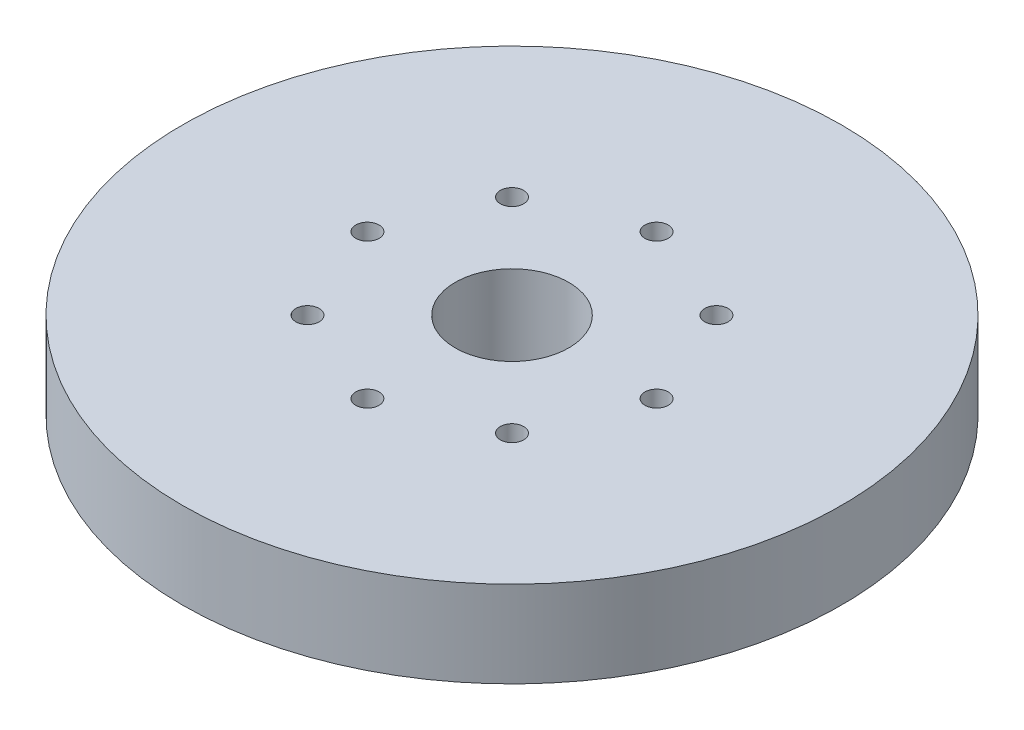
SolidWorks part; units mm, degrees
ref_plane "Front Plane" through (0, 0, 0) normal (0, 0, 1) x (1, 0, 0)
ref_plane "Top Plane" through (0, 0, 0) normal (0, 1, 0) x (1, 0, 0)
ref_plane "Right Plane" through (0, 0, 0) normal (1, 0, 0) x (0, 0, -1)
sketch "Sketch1" plane through (0, 0, 0) normal (0, 1, 0) x (1, 0, 0)
  circle A0 centre (0, 0) radius 72.5
  dimension "FLANGE_OD" = 145
extrude "Boss-Extrude1" add sketch "Sketch1" along normal blind 19
sketch "Sketch2" plane through (0, 0, 0) normal (0, 1, 0) x (1, 0, 0)
  circle A0 centre (0, 0) radius 12.5
  dimension "BORE_D" = 25
extrude "Cut-Extrude1" cut sketch "Sketch2" along normal through all
sketch "Sketch3" plane through (0, 19, 0) normal (0, 1, 0) x (1, 0, 0)
  circle A0 centre (0, 0) radius 31.806 construction
  circle A1 centre (-31.806, 0) radius 2.5629
  dimension "BOLT_D" = 5.1258
  dimension "BOLT_PCD" = 63.612
extrude "Cut-Extrude2" cut sketch "Sketch3" against normal blind 13.8985
pattern_circular "CirPattern1" count 8 over 360 about axis through (0, 0, 0) along (0, 1, 0) of "Cut-Extrude2"
